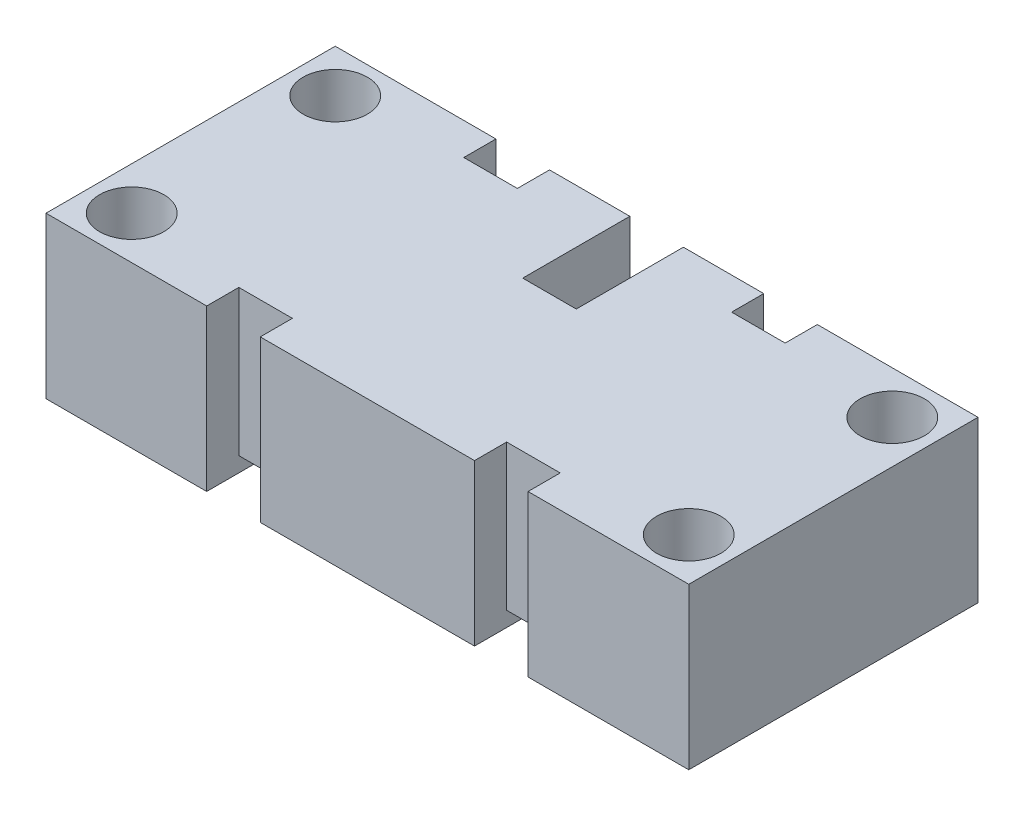
SolidWorks part; units mm, degrees
ref_plane "Front Plane" through (0, 0, 0) normal (0, 0, 1) x (1, 0, 0)
ref_plane "Top Plane" through (0, 0, 0) normal (0, 1, 0) x (1, 0, 0)
ref_plane "Right Plane" through (0, 0, 0) normal (1, 0, 0) x (0, 0, -1)
sketch "Sketch1" plane through (0, 0, 0) normal (0, 1, 0) x (1, 0, 0)
  line L1 (-31.3447, 17.5818) -> (3.5803, 17.5818)
  line L2 (-31.3447, 17.5818) -> (-31.3447, -16.7082)
  line L3 (-31.3447, -16.7082) -> (44.8553, -16.7082)
  line L4 (44.8553, 17.5818) -> (44.8553, -16.7082)
  line L6 (3.5803, 17.5818) -> (3.5803, 4.8818)
  line L7 (3.5803, 4.8818) -> (9.9303, 4.8818)
  line L8 (9.9303, 17.5818) -> (9.9303, 4.8818)
  line L9 (-12.2947, 17.5818) -> (-5.9447, 17.5818)
  line L10 (-12.2947, 17.5818) -> (-12.2947, 13.7718)
  line L11 (-12.2947, 13.7718) -> (-5.9447, 13.7718)
  line L12 (-5.9447, 17.5818) -> (-5.9447, 13.7718)
  line L13 (-31.3447, 0.4368) -> (44.8553, 0.4368) construction
  line L14 (19.4553, 13.7718) -> (25.8053, 13.7718)
  line L15 (25.8053, 13.7718) -> (25.8053, 17.5818)
  line L16 (25.8053, 17.5818) -> (19.4553, 17.5818)
  line L17 (19.4553, 17.5818) -> (19.4553, 13.7718)
  line L18 (-12.2947, -16.7082) -> (-12.2947, -12.8982)
  line L19 (-12.2947, -12.8982) -> (-5.9447, -12.8982)
  line L20 (-5.9447, -16.7082) -> (-5.9447, -12.8982)
  line L21 (19.4553, -16.7082) -> (19.4553, -12.8982)
  line L22 (25.8053, -12.8982) -> (19.4553, -12.8982)
  line L23 (25.8053, -12.8982) -> (25.8053, -16.7082)
  line L24 (25.8053, -16.7082) -> (19.4553, -16.7082)
  line L25 (9.9303, 17.5818) -> (44.8553, 17.5818)
  circle A0 centre (-26.2647, 12.5018) radius 3.81
  circle A1 centre (39.7753, 12.5018) radius 3.81
  circle A2 centre (-26.2647, -11.6282) radius 3.81
  circle A3 centre (39.7753, -11.6282) radius 3.81
  circle A4 centre (-26.2647, 12.5018) radius 2.159
  circle A5 centre (-26.2647, -11.6282) radius 2.159
  circle A6 centre (39.7753, -11.6282) radius 2.159
  circle A7 centre (39.7753, 12.5018) radius 2.159
  point P25 (0, 0)
  point P26 (0, 0)
  point P27 (19.4553, 13.7718)
  point P28 (19.4553, 17.5818)
  point P29 (25.8053, 17.5818)
  point P30 (25.8053, 13.7718)
  point P44 (25.8053, -16.7082)
  point P45 (24.8596, -16.7082)
  dimension "D1" = 76.2
  dimension "D5" = 7.62
  dimension "D6" = 7.62
  dimension "D7" = 7.62
  dimension "D8" = 7.62
  dimension "D9" = 4.318
  dimension "D10" = 4.318
  dimension "D11" = 4.318
  dimension "D12" = 4.318
  dimension "D2" = 34.29
  dimension "D3" = 6.35
  dimension "D4" = 34.925
  dimension "D13" = 5.08
  dimension "D14" = 5.08
  dimension "D15" = 5.08
  dimension "D16" = 5.08
  dimension "D17" = 5.08
  dimension "D18" = 5.08
  dimension "D19" = 5.08
  dimension "D20" = 5.08
  dimension "D21" = 3.81
  dimension "D22" = 6.35
  dimension "D23" = 12.7
  dimension "D24" = 25.4
  dimension "D25" = 25.4
  dimension "D26" = 25.4
  dimension "D27" = 3.81
  dimension "D28" = 6.35
  dimension "D29" = 6.35
extrude "Boss-Extrude1" add sketch "Sketch1" along normal blind 19.05 contours L22 L23 L3 L4 L1 L15 L14 L17 L12 L11 L10 L2 L18 L19 L20 L21 A3 A2 A1 A0 L8 L7 L6 | L13 L2 L3 L18 L19 L20 L21 L22 L23 L4 A3 A2 region at (-21.8197, 0, -16.8008) region at (6.7553, 0, 7.5862)
extrude "Boss-Extrude2" add sketch "Sketch1<3>" along normal blind 2.54 contours A0 A4 | A2 A5 | A1 A7 | A3 A6 region at (-29.9669, 0, -12.5018) region at (36.0731, 0, -12.5018) region at (-29.9669, 0, 11.6282) region at (36.0731, 0, 11.6282)
sketch "Sketch1<3>" plane through (0, 0, 0) normal (0, 1, 0) x (1, 0, 0) same geometry as "Sketch1"
sketch "Sketch2" plane through (0, 0, 16.7082) normal (0, 0, 1) x (1, 0, 0)
  line L0 (-5.9447, 19.05) -> (-5.9447, 0) construction
  line L1 (-12.2947, 0) -> (-5.9447, 0)
  line L2 (-12.2947, 0) -> (-12.2947, 1.778)
  line L3 (-12.2947, 1.778) -> (-5.9447, 1.778)
  line L4 (-5.9447, 0) -> (-5.9447, 1.778)
  line L5 (25.8053, 19.05) -> (25.8053, 0) construction
  line L6 (19.4553, 0) -> (25.8053, 0)
  line L7 (19.4553, 0) -> (19.4553, 1.778)
  line L8 (19.4553, 1.778) -> (25.8053, 1.778)
  line L9 (25.8053, 0) -> (25.8053, 1.778)
  line M4 (19.4553, 0) -> (19.4553, 19.05)
  line M6 (-5.9447, 19.05) -> (-5.9447, 0)
  dimension "D1" = 1.778
  dimension "D2" = 1.778
extrude "Cut-Extrude2" cut sketch "Sketch2" against normal through all contours L3 L2 L1 M6 | L6 L9 L8 M4 region at (-9.1197, 0.889, 16.7082) region at (22.6303, 0.889, 16.7082)
